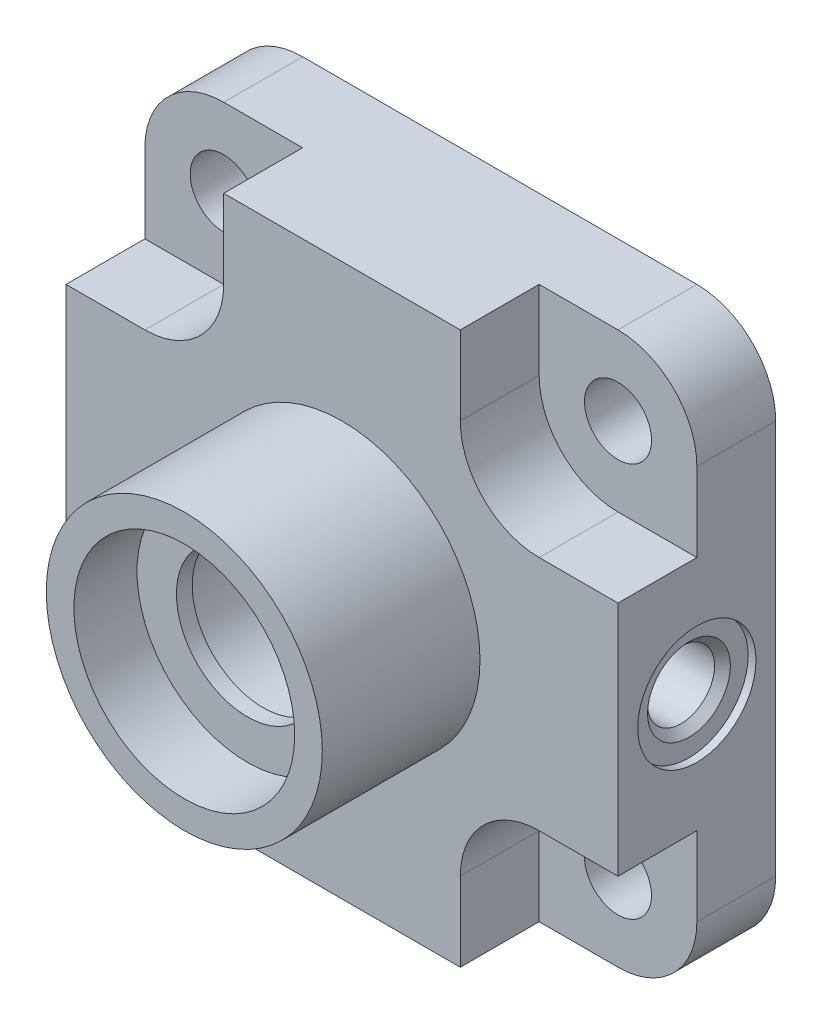
SolidWorks part; units mm, degrees
ref_plane "Front Plane" through (0, 0, 0) normal (0, 0, 1) x (1, 0, 0)
ref_plane "Top Plane" through (0, 0, 0) normal (0, 1, 0) x (1, 0, 0)
ref_plane "Right Plane" through (0, 0, 0) normal (1, 0, 0) x (0, 0, -1)
sketch "Sketch2" plane through (0, 0, 0) normal (0, 0, 1) x (1, 0, 0)
  line L1 (35, -35) -> (-35, -35)
  line L2 (35, -35) -> (35, 35)
  line L3 (35, 35) -> (-35, 35)
  line L4 (-35, -35) -> (-35, 35)
  line L5 (35, -35) -> (-35, 35) construction
  line L6 (35, 35) -> (-35, -35) construction
  point P0 (0, 0)
  dimension "D1" = 70
  dimension "D2" = 70
extrude "Boss-Extrude1" add sketch "Sketch2" along normal blind 24
sketch "Sketch3" plane through (0, 0, 0) normal (0, 0, -1) x (-1, 0, 0)
  circle A0 centre (0, 0) radius 22
  circle A1 centre (0, 0) radius 16
  circle A2 centre (0, 0) radius 25
  circle A3 centre (0, 0) radius 55
  line M1 (35, -35) -> (35, 35)
  line M2 (35, 35) -> (-35, 35)
  line M3 (-35, 35) -> (-35, -35)
  line M4 (-35, -35) -> (35, -35)
  dimension "D1" = 44
  dimension "D2" = 32
  dimension "D3" = 50
  dimension "D4" = 110
extrude "Cut-Extrude1" cut sketch "Sketch3" against normal blind 4 contours A3 M1 M4 M3 M2 | A0 A1 region at (21.3777, 0, 0) region at (53.4444, 0, 0)
extrude "Cut-Extrude2" cut sketch "Sketch3<3>" against normal blind 4 contours A2 M4 M1 M2 M3 region at (0, -34.0101, 0)
sketch "Sketch3<3>" plane through (0, 0, 0) normal (0, 0, -1) x (-1, 0, 0) same geometry as "Sketch3"
sketch "Sketch4" plane through (0, 0, 24) normal (0, 0, 1) x (1, 0, 0)
  line L0 (-15, 35) -> (-15, 15)
  line L1 (35, 35) -> (-35, 35) construction
  line L2 (-35, 15) -> (-15, 15)
  line L3 (-35, 35) -> (-35, -35) construction
  circle A0 centre (-25, 25) radius 4.25
  line M1 (-35, 35) -> (-35, -35)
  line M4 (35, 35) -> (-35, 35)
  dimension "D3" = 10
  dimension "D5" = 8.5
  dimension "D1" = 20
  dimension "D2" = 20
  dimension "D4" = 10
extrude "Cut-Extrude3" cut sketch "Sketch4" against normal blind 10 contours L2 L0 A0 M1 M4 region at (-15.2828, 25, 24)
extrude "Cut-Extrude4" cut sketch "Sketch4<3>" against normal up to next contours A0 region at (-25, 25, 24)
sketch "Sketch4<3>" plane through (0, 0, 24) normal (0, 0, 1) x (1, 0, 0) same geometry as "Sketch4"
mirror "Mirror1" about plane through (0, 0, 0) normal (0, 1, 0) of "Cut-Extrude4", "Cut-Extrude3"
mirror "Mirror2" about plane through (0, 0, 0) normal (1, 0, 0) of "Mirror1", "Cut-Extrude3", "Cut-Extrude4"
fillet "Fillet1" radius 10 8 edges at (35, 35, 9) (15, 15, 19) (35, -35, 9) (15, -15, 19) (-15, -15, 19) (-35, -35, 9) (-15, 15, 19) (-35, 35, 9)
sketch "Sketch5" plane through (0, 0, 24) normal (0, 0, 1) x (1, 0, 0)
  circle A0 centre (0, 0) radius 17.5
  dimension "D1" = 35
extrude "Boss-Extrude2" add sketch "Sketch5" along normal blind 20
sketch "Sketch6" plane through (0, 0, 44) normal (0, 0, 1) x (1, 0, 0)
  circle A0 centre (0, 0) radius 14
  dimension "D1" = 28
extrude "Cut-Extrude5" cut sketch "Sketch6" against normal blind 8
sketch "Sketch7" plane through (0, 0, 36) normal (0, 0, 1) x (1, 0, 0)
  circle A0 centre (0, 0) radius 9
  dimension "D1" = 18
extrude "Cut-Extrude6" cut sketch "Sketch7" against normal blind 2
sketch "Sketch8" plane through (0, 0, 34) normal (0, 0, 1) x (1, 0, 0)
  circle A0 centre (0, 0) radius 10
  dimension "D1" = 20
extrude "Cut-Extrude7" cut sketch "Sketch8" against normal blind 10
sketch "Sketch9" plane through (0, 0, 24) normal (0, 0, 1) x (1, 0, 0)
  circle A0 centre (0, 0) radius 9
  dimension "D1" = 18
extrude "Cut-Extrude8" cut sketch "Sketch9" against normal blind 4
sketch "Sketch10" plane through (0, 0, 20) normal (0, 0, 1) x (1, 0, 0)
  circle A0 centre (0, 0) radius 10
  dimension "D1" = 20
extrude "Cut-Extrude9" cut sketch "Sketch10" against normal blind 20
sketch "Sketch11" plane through (35, 0, 0) normal (1, 0, 0) x (0, 0, -1)
  line L0 (-4, -25) -> (-4, 25) construction
  circle A0 centre (-14, 0) radius 7.5
  dimension "D1" = 15
  dimension "D2" = 10
extrude "Cut-Extrude10" cut sketch "Sketch11" against normal blind 1
hole_wizard "M10 Tapped Hole1" positions "Sketch13" profile "Sketch12" tap size "M10" standard "DIN" end condition up to next
sketch "Sketch13" plane through (34, 0, 0) normal (1, 0, 0) x (0, 0, -1)
  circle A0 centre (-14, 0) radius 7.5 construction
  point P0 (-14, 0)
sketch "Sketch12" plane through (34, 0, 14) normal (0, 1, 0) x (0, 0, -1)
  line L0 (0, 0) -> (0, 24)
  line L1 (0, 24) -> (4.25, 24)
  line L2 (4.25, 24) -> (4.25, 0)
  line L5 (4.25, 0) -> (0, 0)
  line L11 (0, -6.35) -> (0, 107.95) construction
  dimension "Thru Tap Drill Dia." = 8.5
  dimension "Thru Tap Drill Depth" = 24
cosmetic thread "Hole Thread1" parameters "D2"=10
chamfer "Chamfer1" distance 1 angle 45 1 edges at (34, 0, 9.75)
